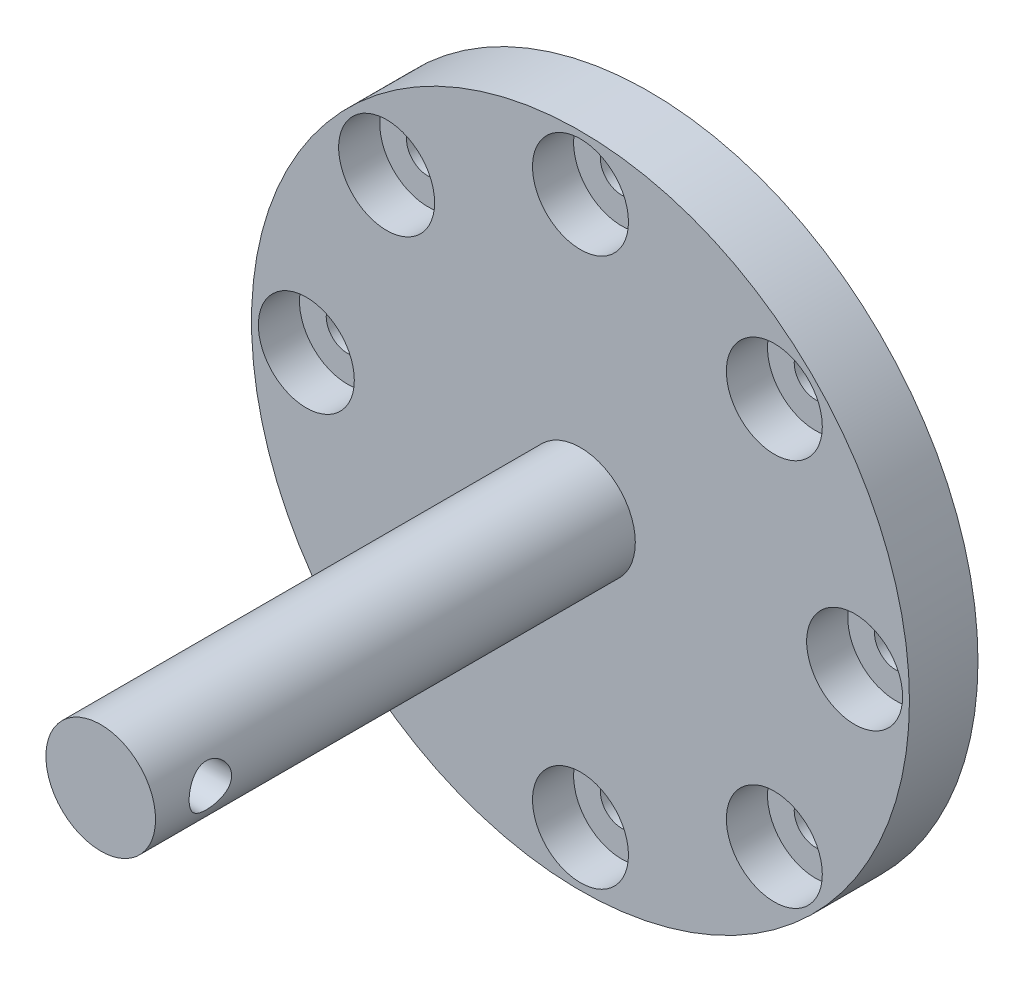
SolidWorks part; units mm, degrees
ref_plane "Front Plane" through (0, 0, 0) normal (0, 0, 1) x (1, 0, 0)
ref_plane "Top Plane" through (0, 0, 0) normal (0, 1, 0) x (1, 0, 0)
ref_plane "Right Plane" through (0, 0, 0) normal (1, 0, 0) x (0, 0, -1)
ref_axis "Axis1" through (0, 0, 5.5) along (0, 0, -1)
sketch "Sketch6" plane through (0, 0, 0) normal (0, 0, 1) x (1, 0, 0)
  circle A0 centre (0, 0) radius 24
extrude "Boss-Extrude1" add sketch "Sketch6" along normal blind 5
sketch "Sketch8" plane through (0, 0, 0) normal (0, 0, -1) x (-1, 0, 0)
  line L0 (0, 20) -> (0, 0) construction
  circle A0 centre (0, 20) radius 1.55
  circle A1 centre (14.1421, 14.1421) radius 1.55
  circle A2 centre (20, 0) radius 1.55
  circle A3 centre (14.1421, -14.1421) radius 1.55
  circle A4 centre (0, -20) radius 1.55
  circle A5 centre (-14.1421, -14.1421) radius 1.55
  circle A6 centre (-20, 0) radius 1.55
  circle A7 centre (-14.1421, 14.1421) radius 1.55
  dimension "D1" = 8
extrude "Cut-Extrude6" cut sketch "Sketch8" against normal up to surface (5 mm away) up to face at (24, 0, 5)
sketch "Sketch10" plane through (0, 0, 5) normal (0, 0, 1) x (1, 0, 0)
  circle A0 centre (0, 0) radius 4
extrude "Boss-Extrude2" add sketch "Sketch10" along normal blind 35
sketch "Sketch11" plane through (0, 0, 5) normal (0, 0, 1) x (1, 0, 0)
  circle A0 centre (0, 20) radius 3.5
  circle A1 centre (14.1421, 14.1421) radius 3.5
  circle A2 centre (20, 0) radius 3.5
  circle A3 centre (14.1421, -14.1421) radius 3.5
  circle A4 centre (0, -20) radius 3.5
  circle A5 centre (-14.1421, -14.1421) radius 3.5
  circle A6 centre (-20, 0) radius 3.5
  circle A7 centre (-14.1421, 14.1421) radius 3.5
  point P19 (0, 0)
  dimension "D1" = 8
extrude "Cut-Extrude8" cut sketch "Sketch11" against normal blind 3
ref_plane "Plane1" through (0, 0, 0) normal (1, 0, 0) x (0, 0, -1)
sketch "Sketch12" plane through (0, 0, 0) normal (1, 0, 0) x (0, 0, -1)
  line L0 (-40, 0) -> (-36, 0) construction
  line L1 (-40, 4) -> (-40, -4) construction
  circle A0 centre (-36, 0) radius 1.55
extrude "Cut-Extrude9" cut sketch "Sketch12" against normal up to surface and the other way up to surface up to face at (4, 0, 40) other way up to face at (4, 0, 40)
